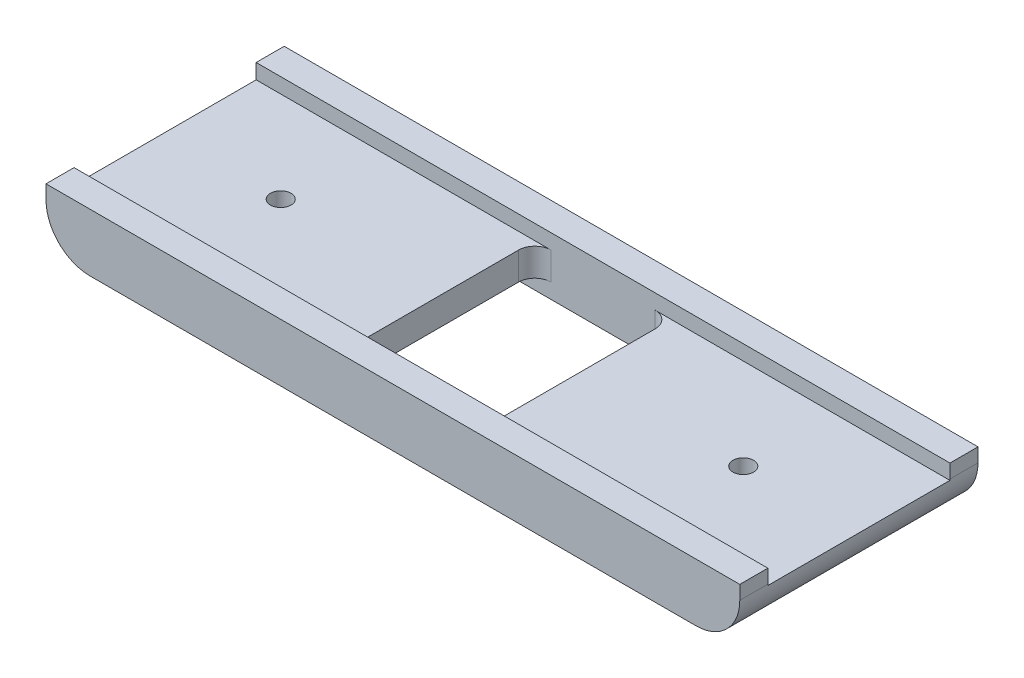
SolidWorks part; units mm, degrees
material "1060 Alloy"
ref_plane "Front Plane" through (0, 0, 0) normal (0, 0, 1) x (1, 0, 0)
ref_plane "Top Plane" through (0, 0, 0) normal (0, 1, 0) x (1, 0, 0)
ref_plane "Right Plane" through (0, 0, 0) normal (1, 0, 0) x (0, 0, -1)
sketch "Sketch1" plane through (0, 0, 0) normal (0, 1, 0) x (1, 0, 0)
  line L0 (-38.1, -13.081) -> (38.1, 13.081) construction
  line L1 (-38.1, 13.081) -> (38.1, 13.081)
  line L2 (-38.1, 13.081) -> (-38.1, -13.081)
  line L3 (-38.1, -13.081) -> (38.1, -13.081)
  line L4 (38.1, 13.081) -> (38.1, -13.081)
  line L5 (-38.1, 13.081) -> (38.1, -13.081) construction
  line L11 (38.1, -26.67) -> (38.1, -10) construction
  line L12 (-38.1, -10) -> (-38.1, -26.67) construction
  point P0 (0, 0)
  point P10 (0, 0)
  dimension "D1" = 26.162
extrude "Boss-Extrude1" add sketch "Sketch1" along normal blind 6.35
fillet "Fillet1" radius 4.826 2 edges at (38.1, 0, 0) (-38.1, 0, 0)
sketch "Sketch2" plane through (38.1, 0, 0) normal (1, 0, 0) x (0, 0, -1)
  line L0 (-10, 0) -> (-10, 1.651)
  line L1 (-13.081, 0) -> (13.081, 0) construction
  line L2 (-10, 1.651) -> (10, 1.651)
  line L3 (10, 1.651) -> (10, 0)
  line L7 (-10, 0) -> (10, 0)
  line L8 (-10, -1.851) -> (-10, -0.2) construction
  line L9 (10, -1.851) -> (10, -0.2) construction
extrude "Cut-Extrude1" cut sketch "Sketch2" against normal through all
sketch "Sketch3" plane through (0, 1.651, 0) normal (0, -1, 0) x (1, 0, 0)
  line L0 (5.722, -10) -> (-5.722, -10) construction
  line L1 (7.5, 8.222) -> (7.5, -8.222) construction
  line L2 (-5.722, 10) -> (5.722, 10) construction
  line L3 (-7.5, -8.222) -> (-7.5, 8.222) construction
  line L4 (5.722, -10) -> (-5.722, -10)
  line L5 (7.5, 8.222) -> (7.5, -8.222)
  line L6 (-5.722, 10) -> (5.722, 10)
  line L7 (-7.5, -8.222) -> (-7.5, 8.222)
  arc A0 (5.722, -10) -> (7.5, -8.222) centre (5.722, -8.222) ccw construction
  arc A1 (7.5, 8.222) -> (5.722, 10) centre (5.722, 8.222) ccw construction
  arc A2 (-5.722, 10) -> (-7.5, 8.222) centre (-5.722, 8.222) ccw construction
  arc A3 (-7.5, -8.222) -> (-5.722, -10) centre (-5.722, -8.222) ccw construction
  arc A4 (5.722, -10) -> (7.5, -8.222) centre (5.722, -8.222) ccw
  arc A5 (7.5, 8.222) -> (5.722, 10) centre (5.722, 8.222) ccw
  arc A6 (-5.722, 10) -> (-7.5, 8.222) centre (-5.722, 8.222) ccw
  arc A7 (-7.5, -8.222) -> (-5.722, -10) centre (-5.722, -8.222) ccw
extrude "Cut-Extrude2" cut sketch "Sketch3" against normal through all and the other way through all
hole_wizard "#4-40 Tapped Hole1" positions "Sketch6" profile "Sketch7" tap size "#4-40" standard "Ansi Inch" end condition through all
sketch "Sketch6" plane through (0, 6.35, 0) normal (0, 1, 0) x (-1, 0, 0)
  point P1 (25.4, 0)
  point P4 (-25.4, 0)
sketch "Sketch7" plane through (-25.4, 6.35, 0) normal (1, 0, 0) x (0, 0, 1)
  line L0 (0, 0) -> (0, 6.35)
  line L1 (0, 6.35) -> (1.1303, 6.35)
  line L2 (1.1303, 6.35) -> (1.1303, 0)
  line L5 (1.1303, 0) -> (0, 0)
  line L11 (0, -6.35) -> (0, 107.95) construction
  dimension "Thru Tap Drill Dia." = 2.2606
  dimension "Thru Tap Drill Depth" = 6.35
cosmetic thread "Hole Thread1" parameters "D2"=2.8448
cosmetic thread "Hole Thread2" parameters "D2"=2.8448
sketch "Sketch8" plane through (38.1, 0, 0) normal (1, 0, 0) x (0, 0, -1)
  line L0 (-10, 6.35) -> (-10, 4.699)
  line L1 (-10, 4.699) -> (10, 4.699)
  line L2 (10, 4.699) -> (10, 6.35)
  line L3 (-13.081, 6.35) -> (13.081, 6.35) construction
  line L4 (10, 6.35) -> (-10, 6.35)
  line L5 (10, 1.651) -> (10, 0) construction
extrude "Cut-Extrude3" cut sketch "Sketch8" against normal through all
